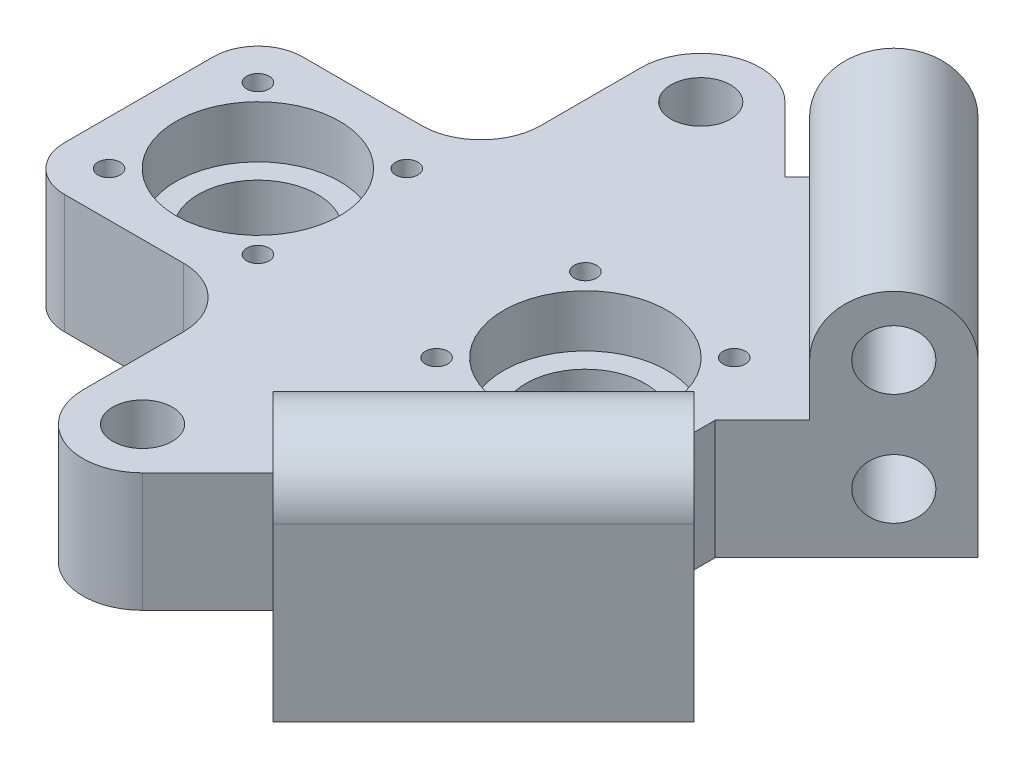
SolidWorks part; units mm, degrees
material "ABS"
ref_plane "Front Plane" through (0, 0, 0) normal (0, 0, 1) x (1, 0, 0)
ref_plane "Top Plane" through (0, 0, 0) normal (0, 1, 0) x (1, 0, 0)
ref_plane "Right Plane" through (0, 0, 0) normal (1, 0, 0) x (0, 0, -1)
sketch "Sketch1" plane through (0, 0, 0) normal (0, 1, 0) x (1, 0, 0)
  line L0 (-386.3027, 0) -> (412.614, 0) construction
  line L1 (0, -323.8826) -> (0, 265.8262) construction
  line L2 (0, 251.091) -> (251.091, 0)
  line L3 (160, 0) -> (80, 138.5641)
  line L4 (160, 0) -> (0, 0)
  line L5 (0, 239.7773) -> (239.7773, 0)
  line L6 (196.4046, 34.4091) -> (187.6569, 43.1569)
  line L7 (144, -10) -> (144, 10)
  line L8 (150, 16) -> (166, 16)
  line L9 (174, 24) -> (174, 37.5)
  line L11 (196.4046, 34.4091) -> (209.3717, 47.3762)
  line L12 (209.3717, 47.3762) -> (237.6559, 19.0919)
  line L13 (237.6559, 19.0919) -> (220, 1.4359)
  line L14 (220, 1.4359) -> (220, -1.4359)
  line L15 (237.6559, -19.0919) -> (220, -1.4359)
  line L16 (209.3717, -47.3762) -> (237.6559, -19.0919)
  line L17 (196.4046, -34.4091) -> (209.3717, -47.3762)
  line L18 (187.6569, -43.1569) -> (196.4046, -34.4091)
  line L19 (174, -24) -> (174, -37.5)
  line L20 (150, -16) -> (166, -16)
  circle A0 centre (0, 0) radius 160
  circle A1 centre (160, 0) radius 11
  circle A2 centre (150, 10) radius 1.5
  circle A3 centre (170, 10) radius 1.5
  circle A4 centre (170, -10) radius 1.5
  circle A5 centre (150, -10) radius 1.5
  circle A6 centre (204, 0) radius 11
  circle A7 centre (182, 37.5) radius 4
  circle A8 centre (80, 138.5641) radius 15
  circle A9 centre (194, 10) radius 1.5
  circle A10 centre (214, 10) radius 1.5
  circle A11 centre (214, -10) radius 1.5
  circle A12 centre (194, -10) radius 1.5
  arc A13 (144, 10) -> (150, 16) centre (150, 10) cw
  arc A14 (174, 37.5) -> (187.6569, 43.1569) centre (182, 37.5) cw
  arc A15 (166, 16) -> (174, 24) centre (166, 24) ccw
  circle A16 centre (182, -37.5) radius 4
  arc A17 (174, -37.5) -> (187.6569, -43.1569) centre (182, -37.5) ccw
  arc A18 (166, -16) -> (174, -24) centre (166, -24) cw
  arc A19 (144, -10) -> (150, -16) centre (150, -10) ccw
  circle A20 centre (160, 0) radius 8
  circle A21 centre (204, 0) radius 8
  point P53 (220, 0)
  point P65 (144, 0)
  dimension "D1" = 320
  dimension "D2" = 22
  dimension "D5" = 3
  dimension "D10" = 22
  dimension "D13" = 30
  dimension "D11" = 8
  dimension "D14" = 8
  dimension "D18" = 3
  dimension "D25" = 6
  dimension "D28" = 8
  dimension "D33" = 16
  dimension "D34" = 16
  dimension "D3" = 10
  dimension "D4" = 10
  dimension "D8" = 45
  dimension "D9" = 160
  dimension "D12" = 37.5
  dimension "D15" = 15
  dimension "D16" = 44
  dimension "D17" = 22
  dimension "D19" = 10
  dimension "D20" = 10
  dimension "D23" = 16
  dimension "D24" = 16
  dimension "D26" = 8
  dimension "D29" = 4
  dimension "D31" = 16
  dimension "D32" = 40
  dimension "D6" = 2
  dimension "D7" = 2
  dimension "D21" = 2
  dimension "D22" = 2
extrude "Boss-Extrude1" add sketch "Sketch1" along normal blind 16 contours L20 A18 L19 A17 L18 L17 L16 L15 L14 L13 L5 L11 A14 L9 A15 L8 A0 A1 A16 A12 A11 A10 A9 A7 A6 A4 A3 | A13 L7 L4 A1 L3 L8 A2 | A1 A0 L8 L3 | L7 A19 L20 A0 A1 L4 A5 | L13 L2 L11 L5 | L13 L12 L11 L2 region at (222.0996, 0, -31.8198) region at (217.857, 0, -27.5772) region at (214.1688, 0, -23.889) region at (154.599, 0, 15.7764) region at (155.7484, 0, -13.3869) region at (147.953, 0, -8.215)
extrude "Boss-Extrude2" add sketch "Sketch1<4>" along normal blind 9 contours A6 A21 region at (193.3111, 0, 0)
sketch "Sketch1<4>" plane through (0, 0, 0) normal (0, 1, 0) x (1, 0, 0) same geometry as "Sketch1"
sketch "Sketch2" plane through (109.282, 0, 109.282) normal (0.7071, 0, 0.7071) x (0.7071, 0, -0.7071)
  line L0 (181.5481, 16) -> (156.5789, 16) construction
  line L1 (181.5481, 16) -> (181.5481, 0) construction
  circle A0 centre (173.5481, 8) radius 4
  dimension "D1" = 8
  dimension "D2" = 8
  dimension "D3" = 8
extrude "Cut-Extrude1" cut sketch "Sketch2" against normal through all
sketch "Sketch3" plane through (109.282, 0, -109.282) normal (0.7071, 0, -0.7071) x (-0.7071, 0, -0.7071)
  line L0 (-181.5481, 16) -> (-181.5481, 0) construction
  line L1 (-181.5481, 0) -> (-156.5789, 0) construction
  circle A0 centre (-173.5481, 8) radius 4
  dimension "D1" = 8
  dimension "D2" = 8
  dimension "D3" = 8
extrude "Cut-Extrude2" cut sketch "Sketch3" against normal through all
ref_point "Point1"
extrude "Boss-Extrude3" add sketch "Sketch1<5>" along normal blind 9 contours A20 A0 A1 | A20 L4 A1 A0 | A20 L3 A1 L4 | A20 A0 A1 L3 region at (153.7862, 0, 6.029) region at (159.9652, 0, 9.5106) region at (157.4093, 0, -9.1164) region at (152.0783, 0, -4.5736)
sketch "Sketch1<5>" plane through (0, 0, 0) normal (0, 1, 0) x (1, 0, 0) same geometry as "Sketch1"
sketch "Sketch4" plane through (0, 0, 0) normal (0, -1, 0) x (1, 0, 0)
  line L1 (153.4641, 10) -> (151.7321, 13)
  line L2 (151.7321, 13) -> (148.2679, 13)
  line L3 (148.2679, 13) -> (146.5359, 10)
  line L4 (146.5359, 10) -> (148.2679, 7)
  line L5 (148.2679, 7) -> (151.7321, 7)
  line L6 (151.7321, 7) -> (153.4641, 10)
  line L7 (173.4641, 10) -> (171.7321, 13)
  line L8 (171.7321, 13) -> (168.2679, 13)
  line L9 (168.2679, 13) -> (166.5359, 10)
  line L10 (166.5359, 10) -> (168.2679, 7)
  line L11 (168.2679, 7) -> (171.7321, 7)
  line L12 (171.7321, 7) -> (173.4641, 10)
  line L13 (153.4641, -10) -> (151.7321, -7)
  line L14 (151.7321, -7) -> (148.2679, -7)
  line L15 (148.2679, -7) -> (146.5359, -10)
  line L16 (146.5359, -10) -> (148.2679, -13)
  line L17 (148.2679, -13) -> (151.7321, -13)
  line L18 (151.7321, -13) -> (153.4641, -10)
  line L19 (173.4641, -10) -> (171.7321, -7)
  line L20 (171.7321, -7) -> (168.2679, -7)
  line L21 (168.2679, -7) -> (166.5359, -10)
  line L22 (166.5359, -10) -> (168.2679, -13)
  line L23 (168.2679, -13) -> (171.7321, -13)
  line L24 (171.7321, -13) -> (173.4641, -10)
  line L25 (197.4641, 10) -> (195.7321, 13)
  line L26 (195.7321, 13) -> (192.2679, 13)
  line L27 (192.2679, 13) -> (190.5359, 10)
  line L28 (190.5359, 10) -> (192.2679, 7)
  line L29 (192.2679, 7) -> (195.7321, 7)
  line L30 (195.7321, 7) -> (197.4641, 10)
  line L31 (217.4641, 10) -> (215.7321, 13)
  line L32 (215.7321, 13) -> (212.2679, 13)
  line L33 (212.2679, 13) -> (210.5359, 10)
  line L34 (210.5359, 10) -> (212.2679, 7)
  line L35 (212.2679, 7) -> (215.7321, 7)
  line L36 (215.7321, 7) -> (217.4641, 10)
  line L37 (197.4641, -10) -> (195.7321, -7)
  line L38 (195.7321, -7) -> (192.2679, -7)
  line L39 (192.2679, -7) -> (190.5359, -10)
  line L40 (190.5359, -10) -> (192.2679, -13)
  line L41 (192.2679, -13) -> (195.7321, -13)
  line L42 (195.7321, -13) -> (197.4641, -10)
  line L43 (217.4641, -10) -> (215.7321, -7)
  line L44 (215.7321, -7) -> (212.2679, -7)
  line L45 (212.2679, -7) -> (210.5359, -10)
  line L46 (210.5359, -10) -> (212.2679, -13)
  line L47 (212.2679, -13) -> (215.7321, -13)
  line L48 (215.7321, -13) -> (217.4641, -10)
  circle A0 centre (150, 10) radius 3 construction
  circle A1 centre (170, 10) radius 3 construction
  circle A2 centre (150, -10) radius 3 construction
  circle A3 centre (170, -10) radius 3 construction
  circle A4 centre (194, 10) radius 3 construction
  circle A5 centre (214, 10) radius 3 construction
  circle A6 centre (194, -10) radius 3 construction
  circle A7 centre (214, -10) radius 3 construction
extrude "Cut-Extrude3" cut sketch "Sketch4" against normal blind 2.5
sketch "Sketch5" plane through (80.9978, 0, -80.9978) normal (-0.7071, 0, 0.7071) x (0.7071, 0, 0.7071)
  line L0 (181.5481, 16) -> (181.5481, 23)
  line L1 (165.5481, 23) -> (165.5481, 16)
  line L2 (163.2099, 16) -> (181.5481, 16) construction
  line L3 (165.5481, 16) -> (181.5481, 16)
  circle A0 centre (173.5481, 23) radius 4
  circle A1 centre (173.5481, 8) radius 4 construction
  arc A2 (181.5481, 23) -> (165.5481, 23) centre (173.5481, 23) ccw
  dimension "D1" = 8
  dimension "D3" = 8
  dimension "D2" = 15
sketch "Sketch6" plane through (80.9978, 0, 80.9978) normal (-0.7071, 0, -0.7071) x (-0.7071, 0, 0.7071)
  line L0 (-165.5481, 16) -> (-165.5481, 23)
  line L1 (-181.5481, 23) -> (-181.5481, 16)
  line L2 (-181.5481, 16) -> (-165.5481, 16)
  circle A0 centre (-173.5481, 23) radius 4
  arc A1 (-165.5481, 23) -> (-181.5481, 23) centre (-173.5481, 23) ccw
  circle A2 centre (-173.5481, 8) radius 4 construction
  dimension "D1" = 8
  dimension "D2" = 8
  dimension "D3" = 15
extrude "Boss-Extrude4" add sketch "Sketch5" against normal up to surface (40 mm away) up to face at (229.1707, 8, 10.6066)
extrude "Boss-Extrude5" add sketch "Sketch6" against normal up to surface (40 mm away) up to face at (234.8275, 8, -16.2635)
equation "\"rod_diameter\"= 8"
equation "\"rod_hole_thickness\"= 4"
equation "\"rod_radius\"= \"rod_diameter\" / 2"
equation "\"platter_diameter\"= 320"
equation "\"platter_radius\"= \"platter_diameter\" / 2"
equation "\"extruder_mount_hole_spacing\"= 50"
equation "\"arm_rod_spacing\"= 40"
equation "\"D1@Sketch1\"=\"platter_diameter\""
equation "\"D9@Sketch1\"=\"platter_radius\""
equation "\"D11@Sketch1\"=\"rod_diameter\""
equation "\"D14@Sketch1\"=\"rod_diameter\""
equation "\"D12@Sketch1\"=\"z_rod_spacing\"/2"
equation "\"D26@Sketch1\"=\"rod_radius\"+\"rod_hole_thickness\""
equation "\"D28@Sketch1\"=\"rod_radius\"+\"rod_hole_thickness\""
equation "\"D29@Sketch1\"=\"rod_hole_thickness\""
equation "\"D1@Boss-Extrude2\"= \"D1@Boss-Extrude1\" - 7"
equation "\"D1@Sketch2\" = \"rod_diameter\""
equation "\"D2@Sketch2\"= \"D1@Boss-Extrude1\" / 2"
equation "\"D3@Sketch2\"=\"rod_radius\"+\"rod_hole_thickness\""
equation "\"D1@Sketch3\"=\"rod_diameter\""
equation "\"D2@Sketch3\"=\"rod_radius\"+\"rod_hole_thickness\""
equation "\"D3@Sketch3\"= \"D1@Boss-Extrude1\" / 2"
equation "\"D1@Boss-Extrude1\" = \"rod_diameter\" + \"rod_hole_thickness\" * 2"
equation "\"D1@Boss-Extrude3\"= \"D1@Boss-Extrude1\" - 7"
equation "\"D1@Sketch5\"=\"rod_diameter\""
equation "\"top_frame_rod_spacing\"= \"arm_rod_spacing\" + 40"
equation "\"motor_level_rod_spacing\"= 15"
equation "\"D2@Sketch5\"=\"motor_level_rod_spacing\""
equation "\"D3@Sketch5\"=\"rod_radius\"+\"rod_hole_thickness\""
equation "\"D3@Sketch6\"=\"motor_level_rod_spacing\""
equation "\"D1@Sketch6\"=\"rod_diameter\""
equation "\"D2@Sketch6\"=\"rod_radius\"+\"rod_hole_thickness\""
equation "\"linear_bearing_diameter\"= 15"
equation "\"platter_rod_spacing\"= 50"
equation "\"z_rod_spacing\"= 75"
